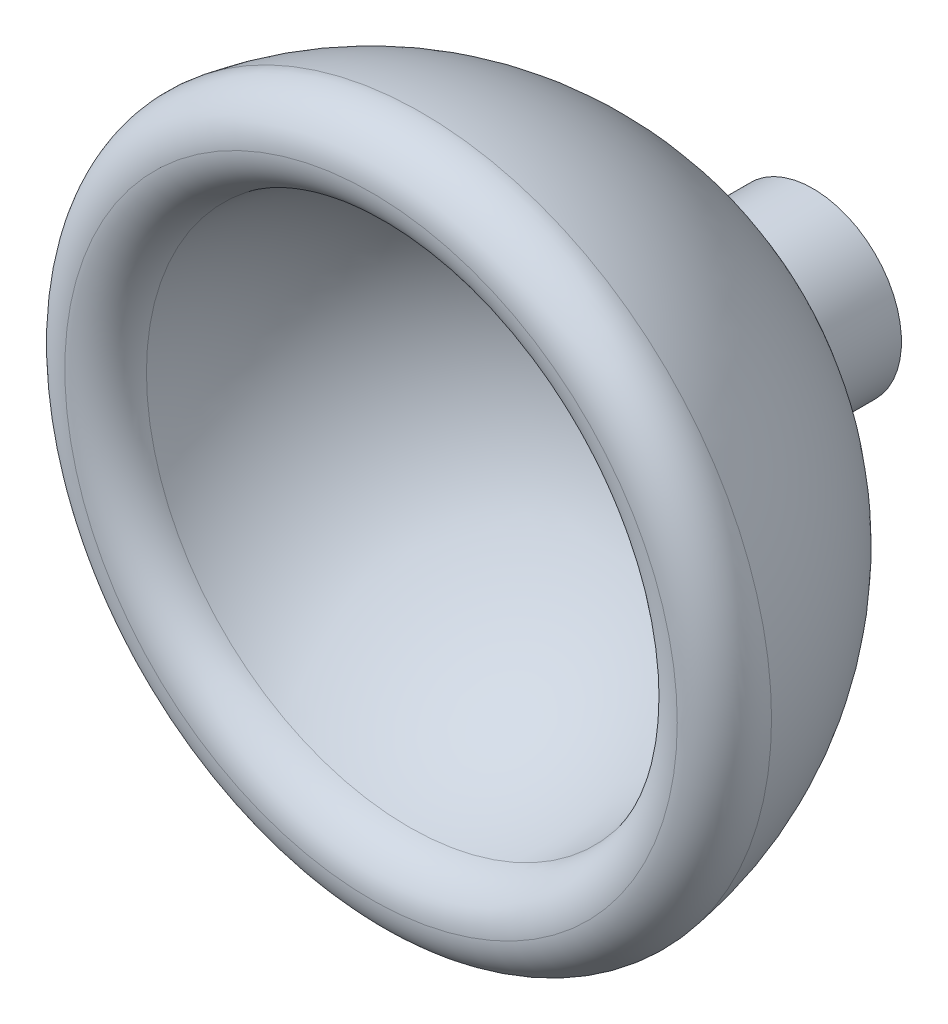
SolidWorks part; units mm, degrees
ref_plane "Front Plane" through (0, 0, 0) normal (0, 0, 1) x (1, 0, 0)
ref_plane "Top Plane" through (0, 0, 0) normal (0, 1, 0) x (1, 0, 0)
ref_plane "Right Plane" through (0, 0, 0) normal (1, 0, 0) x (0, 0, -1)
sketch "Sketch1" plane through (0, 0, 0) normal (0, 1, 0) x (1, 0, 0)
  line L0 (0, 0) -> (0, 40) construction
  line L1 (0, 0) -> (40, 0) construction
  line L2 (0, 40) -> (0, 30)
  line L3 (40, 0) -> (30, 0)
  line L4 (0, 50) -> (0, 40)
  line L5 (0, 50) -> (10, 50)
  line L6 (10, 50) -> (10, 38.7298)
  arc A0 (10, 38.7298) -> (40, 0) centre (0, 0) cw
  arc A1 (0, 30) -> (30, 0) centre (0, 0) cw
  dimension "D3" = 10
  dimension "D7" = 40
  dimension "D1" = 40
  dimension "D2" = 40
  dimension "D4" = 10
  dimension "D5" = 10
  dimension "D6" = 10
revolve "Revolve4" add sketch "Sketch1" angle 360 about L4
fillet "Fillet3" radius 5 2 edges at (-30, 0, 0) (-40, 0, 0)
